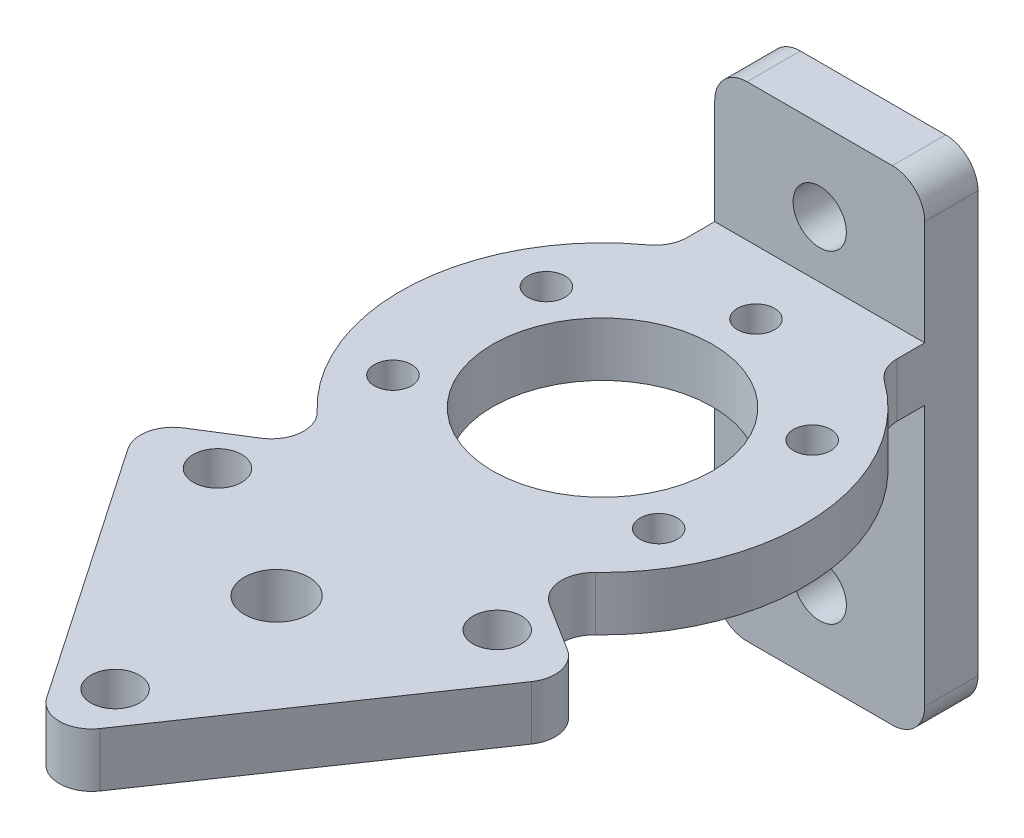
SolidWorks part; units mm, degrees
material "PLA"
ref_plane "Plan de face" through (0, 0, 0) normal (0, 0, 1) x (1, 0, 0)
ref_plane "Plan de dessus" through (0, 0, 0) normal (0, 1, 0) x (1, 0, 0)
ref_plane "Plan de droite" through (0, 0, 0) normal (1, 0, 0) x (0, 0, -1)
sketch "Esquisse1" plane through (0, 0, 0) normal (0, 0, 1) x (1, 0, 0)
  line L0 (55, 0) -> (-55, 0) construction
  line L1 (-6.5, -15) -> (6.5, -15)
  line L2 (-6.5, -15) -> (-6.5, 15)
  line L3 (-6.5, 15) -> (6.5, 15)
  line L4 (6.5, -15) -> (6.5, 15)
  line L5 (-6.5, -15) -> (6.5, 15) construction
  line L6 (-6.5, 15) -> (6.5, -15) construction
  circle A0 centre (0, 10) radius 1.65
  circle A1 centre (0, -10) radius 1.65
  point P0 (0, 0)
  dimension "D4" = 3.3
  dimension "D1" = 30
  dimension "D2" = 13
  dimension "D3" = 10
extrude "Boss.-Extru.1" add sketch "Esquisse1" along normal blind 3.3
fillet "Congé1" radius 2 4 edges at (6.5, -15, 1.65) (-6.5, -15, 1.65) (6.5, 15, 1.65) (-6.5, 15, 1.65)
sketch "Esquisse2" plane through (0, 0, 3.3) normal (0, 0, 1) x (1, 0, 0)
  line L0 (6.5, -13) -> (6.5, 13) construction
  line L3 (-6.5, 6.5) -> (6.5, 6.5)
  line L5 (-6.5, 13) -> (-6.5, -13) construction
  line L7 (-6.5, 6.5) -> (-6.5, 3.15)
  line L10 (-6.5, 3.15) -> (6.5, 3.15)
  line L14 (6.5, 6.5) -> (6.5, 3.15)
  point P0 (0, 0)
  point P8 (0, 0)
  dimension "D1" = 3.15
  dimension "D3" = 3.35
extrude "Boss.-Extru.2" add sketch "Esquisse2" along normal blind 2.77
sketch "Esquisse4" plane through (0, 6.5, 0) normal (0, 1, 0) x (1, 0, 0)
  line L1 (-6.5, -6.07) -> (6.5, -6.07)
  line L3 (-6.5, -27.4242) -> (6.5, -27.4242)
  circle A4 centre (0, -16.7471) radius 6.8
  arc A5 (-6.5, -6.07) -> (-6.5, -27.4242) centre (0, -16.7471) ccw
  arc A6 (6.5, -27.4242) -> (6.5, -6.07) centre (0, -16.7471) ccw
  point P25 (0, -16.7471)
  point P28 (0, -16.7471)
  dimension "D2" = 12.5
  dimension "D3" = 13
  dimension "D6" = 6.8
  dimension "D1" = 12.5
extrude "Boss.-Extru.4" add sketch "Esquisse4" against normal up to surface (3.35 mm away) up to face at (0, 3.15, 4.685)
sketch "Esquisse6" plane through (0, 6.5, 0) normal (0, 1, 0) x (1, 0, 0)
  line L2 (0, -16.7471) -> (8.2272, -11.9971) construction
  line L3 (0, -16.7471) -> (-8.2272, -11.9971) construction
  line L4 (0, -16.7471) -> (0, -7.2471) construction
  line L5 (0, -16.7471) -> (-8.2272, -21.4971) construction
  line L6 (0, -16.7471) -> (0, -26.2471) construction
  line L7 (0, -16.7471) -> (8.2272, -21.4971) construction
  circle A0 centre (0, -7.2471) radius 1.15
  circle A1 centre (-8.2272, -11.9971) radius 1.15
  circle A2 centre (8.2272, -11.9971) radius 1.15
  circle A3 centre (-8.2272, -21.4971) radius 1.15
  circle A7 centre (8.2272, -21.4971) radius 1.15
  dimension "D2" = 2.3
  dimension "D5" = 2.3
  dimension "D6" = 2.3
  dimension "D7" = 9.5
  dimension "D14" = 2.3
  dimension "D15" = 2.3
  dimension "D1" = 9.5
  dimension "D3" = 60
  dimension "D4" = 60
  dimension "D8" = 9.5
  dimension "D9" = 60
  dimension "D10" = 60
  dimension "D11" = 9.5
  dimension "D12" = 9.5
  dimension "D13" = 9.5
extrude "Enlèv. mat.-Extru.2" cut sketch "Esquisse6" against normal through all
sketch "Esquisse8" plane through (0, 6.5, 0) normal (0, 1, 0) x (1, 0, 0)
  line L6 (-6.5, -27.4242) -> (6.5, -27.4242) construction
  line L7 (6.5, -27.4242) -> (-6.5, -27.4242)
  line L8 (0, -9.9471) -> (0, -23.5471) construction
  line L9 (0, -36.9271) -> (0, -27.4242) construction
  line L10 (0, -36.9271) -> (8.6603, -31.9271) construction
  line L11 (0, -36.9271) -> (-8.6603, -31.9271) construction
  line L12 (-6.5, -27.4242) -> (-13.6603, -31.9271)
  line L13 (-13.6603, -31.9271) -> (0, -51.9271)
  line L14 (0, -51.9271) -> (13.6603, -31.9271)
  line L15 (13.6603, -31.9271) -> (6.5, -27.4242)
  circle A0 centre (0, -36.9271) radius 2
  circle A1 centre (0, -36.9271) radius 10 construction
  circle A2 centre (8.6603, -31.9271) radius 1.5
  circle A3 centre (0, -16.7471) radius 6.8 construction
  circle A4 centre (-8.6603, -31.9271) radius 1.5
  circle A7 centre (0, -46.9271) radius 1.5
  point P16 (0, -16.7471)
  dimension "D2" = 4
  dimension "D5" = 3
  dimension "D6" = 3
  dimension "D7" = 3
  dimension "D1" = 20.18
  dimension "D3" = 120
  dimension "D4" = 60
  dimension "D8" = 5
  dimension "D9" = 5
  dimension "D10" = 5
  dimension "D11" = 8.6603
extrude "Boss.-Extru.5" add sketch "Esquisse8" against normal up to surface (3.35 mm away) up to face at (0, 3.15, 8.3971)
fillet "Congé2" radius 2 7 edges at (13.6603, 4.825, 31.9271) (0, 4.825, 51.9271) (-13.6603, 4.825, 31.9271) (-6.5, 4.825, 27.4242) (6.5, 4.825, 27.4242) (6.5, 4.825, 6.07) (-6.5, 4.825, 6.07)
